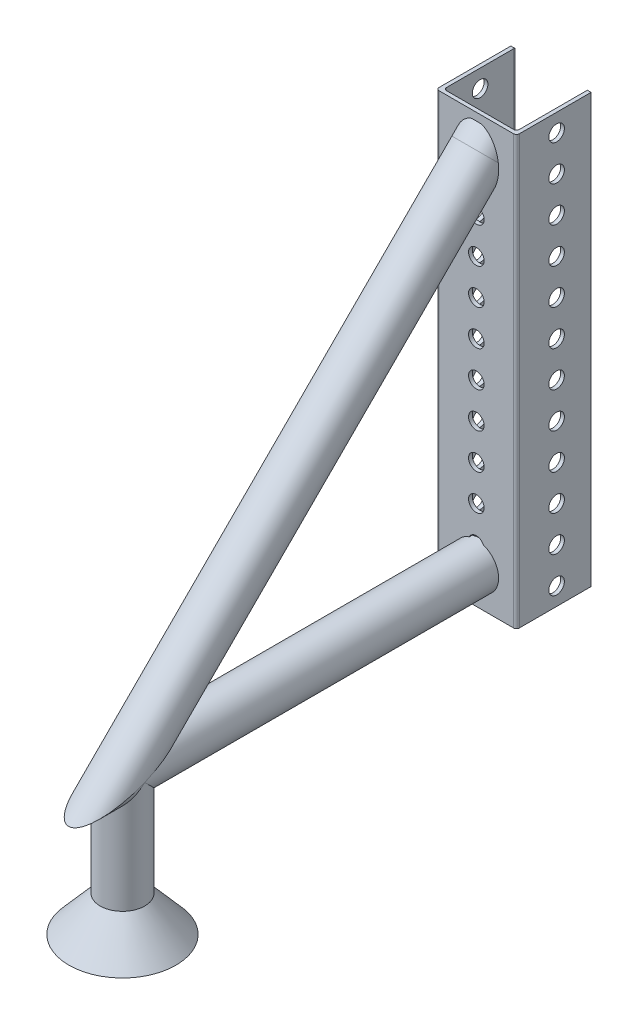
SolidWorks part; units mm, degrees
ref_plane "Front Plane" through (0, 0, 0) normal (0, 0, 1) x (1, 0, 0)
ref_plane "Top Plane" through (0, 0, 0) normal (0, 1, 0) x (1, 0, 0)
ref_plane "Right Plane" through (0, 0, 0) normal (1, 0, 0) x (0, 0, -1)
sketch "Sketch1" plane through (0, 0, 0) normal (0, 1, 0) x (1, 0, 0)
  line L1 (2, 0) -> (55.15, 0)
  line L2 (0, 2) -> (0, 55.15)
  line L3 (2, 57.15) -> (55.15, 57.15)
  line L4 (57.15, 2) -> (57.15, 55.15)
  line L5 (4.667, 54.483) -> (52.483, 54.483)
  line L6 (2.667, 52.483) -> (2.667, 4.667)
  line L7 (4.667, 2.667) -> (52.483, 2.667)
  line L8 (54.483, 52.483) -> (54.483, 4.667)
  arc A0 (55.15, 57.15) -> (57.15, 55.15) centre (55.15, 55.15) cw
  arc A1 (52.483, 54.483) -> (54.483, 52.483) centre (52.483, 52.483) cw
  arc A2 (55.15, 0) -> (57.15, 2) centre (55.15, 2) ccw
  arc A3 (52.483, 2.667) -> (54.483, 4.667) centre (52.483, 4.667) ccw
  arc A4 (2.667, 4.667) -> (4.667, 2.667) centre (4.667, 4.667) ccw
  arc A5 (2, 0) -> (0, 2) centre (2, 2) cw
  arc A6 (4.667, 54.483) -> (2.667, 52.483) centre (4.667, 52.483) ccw
  arc A7 (0, 55.15) -> (2, 57.15) centre (2, 55.15) cw
  point P15 (57.15, 0)
  point P22 (0, 0)
  point P27 (0, 57.15)
  dimension "D7" = 2
  dimension "D1" = 57.15
  dimension "D2" = 57.15
  dimension "D3" = 2.667
  dimension "D4" = 2.667
  dimension "D5" = 2.667
  dimension "D6" = 2.667
extrude "Boss-Extrude1" add sketch "Sketch1" along normal blind 304.8
sketch "Sketch2" plane through (0, 0, 0) normal (0, 0, 1) x (1, 0, 0)
  line L0 (28.575, 304.8) -> (28.575, 0) construction
  line L1 (2, 304.8) -> (55.15, 304.8) construction
  line L2 (2, 0) -> (55.15, 0) construction
  circle A0 centre (28.575, 292.1) radius 5.5563
  circle A1 centre (28.575, 266.7) radius 5.5563
  circle A2 centre (28.575, 241.3) radius 5.5562
  circle A3 centre (28.575, 215.9) radius 5.5562
  circle A4 centre (28.575, 190.5) radius 5.5562
  circle A5 centre (28.575, 165.1) radius 5.5563
  circle A6 centre (28.575, 139.7) radius 5.5563
  circle A7 centre (28.575, 114.3) radius 5.5562
  circle A8 centre (28.575, 88.9) radius 5.5562
  circle A9 centre (28.575, 63.5) radius 5.5562
  circle A10 centre (28.575, 38.1) radius 5.5562
  circle A11 centre (28.575, 12.7) radius 5.5562
  dimension "D1" = 11.1125
  dimension "D3" = 12.7
  dimension "D4" = 12.7
  dimension "D2" = 12
extrude "Cut-Extrude1" cut sketch "Sketch2" against normal blind 304.8
sketch "Sketch3" plane through (57.15, 0, -57.15) normal (-1, 0, 0) x (0, 0, 1)
  line L0 (28.575, 304.8) -> (28.575, 0) construction
  circle A0 centre (28.575, 292.1) radius 5.5563
  circle A1 centre (28.575, 266.7) radius 5.5563
  circle A2 centre (28.575, 241.3) radius 5.5562
  circle A3 centre (28.575, 215.9) radius 5.5562
  circle A4 centre (28.575, 190.5) radius 5.5562
  circle A5 centre (28.575, 165.1) radius 5.5563
  circle A6 centre (28.575, 139.7) radius 5.5563
  circle A7 centre (28.575, 114.3) radius 5.5562
  circle A8 centre (28.575, 88.9) radius 5.5562
  circle A9 centre (28.575, 63.5) radius 5.5562
  circle A10 centre (28.575, 38.1) radius 5.5563
  circle A11 centre (28.575, 12.7) radius 5.5562
  dimension "D1" = 11.1125
  dimension "D2" = 12
extrude "Cut-Extrude2" cut sketch "Sketch3" along normal blind 304.8
sketch "Sketch4" plane through (0, 0, -57.15) normal (0, 0, -1) x (-1, 0, 0)
  line L1 (-57.15, 304.8) -> (0, 304.8)
  line L2 (-57.15, 304.8) -> (-57.15, 0)
  line L3 (-57.15, 0) -> (0, 0)
  line L4 (0, 304.8) -> (0, 0)
extrude "Cut-Extrude3" cut sketch "Sketch4" against normal blind 4
ref_plane "Plane1" through (28.575, 0, 0) normal (1, 0, 0) x (0, 0, -1)
sketch "Sketch5" plane through (28.575, 0, 0) normal (1, 0, 0) x (0, 0, -1)
  line L0 (2, 279.4) -> (-252, 25.4)
  line L2 (2, 304.8) -> (2, 0) construction
  line L3 (-252, 25.4) -> (2, 25.4)
  line L4 (2, 0) -> (53.15, 0) construction
  line L5 (2, 279.4) -> (10.9803, 288.3803)
  dimension "D1" = 45
  dimension "D2" = 254
  dimension "D3" = 25.4
  dimension "D4" = 12.7
sweep "Sweep1" add path "Sketch5" circular profile diameter 31.75 parameters "D3"=31.75
sketch "Sketch18" plane through (0, 0, 0) normal (0, 1, 0) x (1, 0, 0)
  circle A0 centre (28.575, -252) radius 15.875
extrude "Boss-Extrude2" add sketch "Sketch18" along normal up to surface and the other way blind 25.4 up to face at (28.575, 9.525, 290.3256)
sketch "Sketch19" plane through (28.575, 0, 0) normal (1, 0, 0) x (0, 0, -1)
  line L0 (-252, -25.4) -> (-252, -76.2) construction
  line L1 (-267.875, -25.4) -> (-236.125, -25.4) construction
  line L2 (-236.125, -25.4) -> (-236.125, -50.8)
  line L3 (-236.125, -50.8) -> (-213.9, -76.2)
  line L4 (-213.9, -76.2) -> (-252, -76.2)
  line L5 (-236.125, -25.4) -> (-252, -25.4)
  line L6 (-252, -25.4) -> (-252, -76.2)
  dimension "D1" = 38.1
  dimension "D2" = 25.4
  dimension "D3" = 50.8
revolve "Revolve1" add sketch "Sketch19" angle 360 about L0
